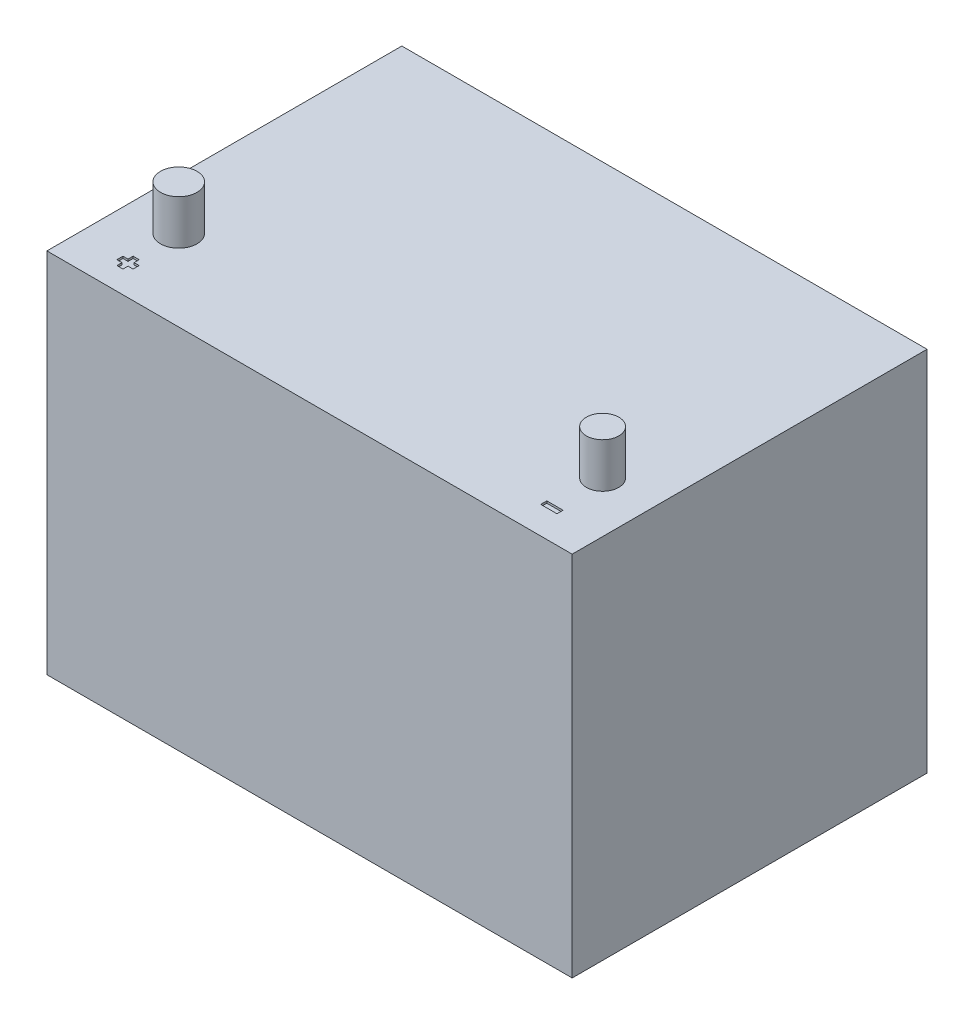
SolidWorks part; units mm, degrees
material "PPE"
ref_plane "Front Plane" through (0, 0, 0) normal (0, 0, 1) x (1, 0, 0)
ref_plane "Top Plane" through (0, 0, 0) normal (0, 1, 0) x (1, 0, 0)
ref_plane "Right Plane" through (0, 0, 0) normal (1, 0, 0) x (0, 0, -1)
sketch "Sketch1" plane through (0, 0, 0) normal (0, 1, 0) x (1, 0, 0)
  line L1 (-129.5, 87.5) -> (129.5, 87.5)
  line L2 (-129.5, 87.5) -> (-129.5, -87.5)
  line L3 (-129.5, -87.5) -> (129.5, -87.5)
  line L4 (129.5, 87.5) -> (129.5, -87.5)
  line L5 (-129.5, 87.5) -> (129.5, -87.5) construction
  line L6 (-129.5, -87.5) -> (129.5, 87.5) construction
  point P0 (0, 0)
  dimension "D1" = 259
  dimension "D2" = 175
extrude "Boss-Extrude1" add sketch "Sketch1" along normal blind 181
sketch "Sketch2" plane through (0, 181, 0) normal (0, 1, 0) x (1, 0, 0)
  line L0 (129.5, -87.5) -> (129.5, 87.5) construction
  line L3 (-129.5, -87.5) -> (129.5, -87.5) construction
  circle A0 centre (-104.5, -47.5) radius 9
  circle A1 centre (104.5, -47.5) radius 8
  point P4 (-104.5, -47.5)
  point P7 (104.5, -47.5)
  dimension "D3" = 18
  dimension "D5" = 16
  dimension "D1" = 25
  dimension "D2" = 209
  dimension "D4" = 40
extrude "Boss-Extrude2" add sketch "Sketch2" along normal blind 22
sketch "Sketch3" plane through (0, 181, 0) normal (0, 1, 0) x (1, 0, 0)
  line L0 (-129.5, 87.5) -> (-129.5, -87.5) construction
  line L1 (-106, -68.5) -> (-103, -68.5)
  line L2 (-106, -68.5) -> (-106, -76.5)
  line L3 (-106, -76.5) -> (-103, -76.5)
  line L4 (-103, -68.5) -> (-103, -76.5)
  line L5 (-106, -68.5) -> (-103, -76.5) construction
  line L6 (-106, -76.5) -> (-103, -68.5) construction
  line L7 (-108.5, -71) -> (-100.5, -71)
  line L8 (-108.5, -71) -> (-108.5, -74)
  line L9 (-108.5, -74) -> (-100.5, -74)
  line L10 (-100.5, -71) -> (-100.5, -74)
  line L11 (-108.5, -71) -> (-100.5, -74) construction
  line L12 (-108.5, -74) -> (-100.5, -71) construction
  line L13 (-129.5, -87.5) -> (129.5, -87.5) construction
  line L14 (129.5, -87.5) -> (129.5, 87.5) construction
  line L15 (100.5, -74) -> (108.5, -74)
  line L16 (100.5, -74) -> (100.5, -71)
  line L17 (100.5, -71) -> (108.5, -71)
  line L18 (108.5, -74) -> (108.5, -71)
  line L19 (100.5, -74) -> (108.5, -71) construction
  line L20 (100.5, -71) -> (108.5, -74) construction
  point P4 (-104.5, -72.5)
  point P9 (-104.5, -72.5)
  point P19 (104.5, -72.5)
  dimension "D1" = 8
  dimension "D2" = 8
  dimension "D3" = 25
  dimension "D4" = 15
  dimension "D5" = 3
  dimension "D6" = 3
  dimension "D7" = 25
  dimension "D8" = 3
  dimension "D9" = 8
  dimension "D10" = 15
extrude "Cut-Extrude1" cut sketch "Sketch3" against normal blind 1 contours L8 L9 L2 L7 | L2 L9 L4 L7 | L2 L7 L4 L1 | L10 L7 L4 L9 | L9 L2 L3 L4 | L15 L18 L17 L16 region at (-104.5, 181, 69.75) region at (-104.5, 181, 72.5) region at (-107.25, 181, 72.5) region at (-101.75, 181, 72.5) region at (-104.5, 181, 75.25) region at (104.5, 181, 72.5)
